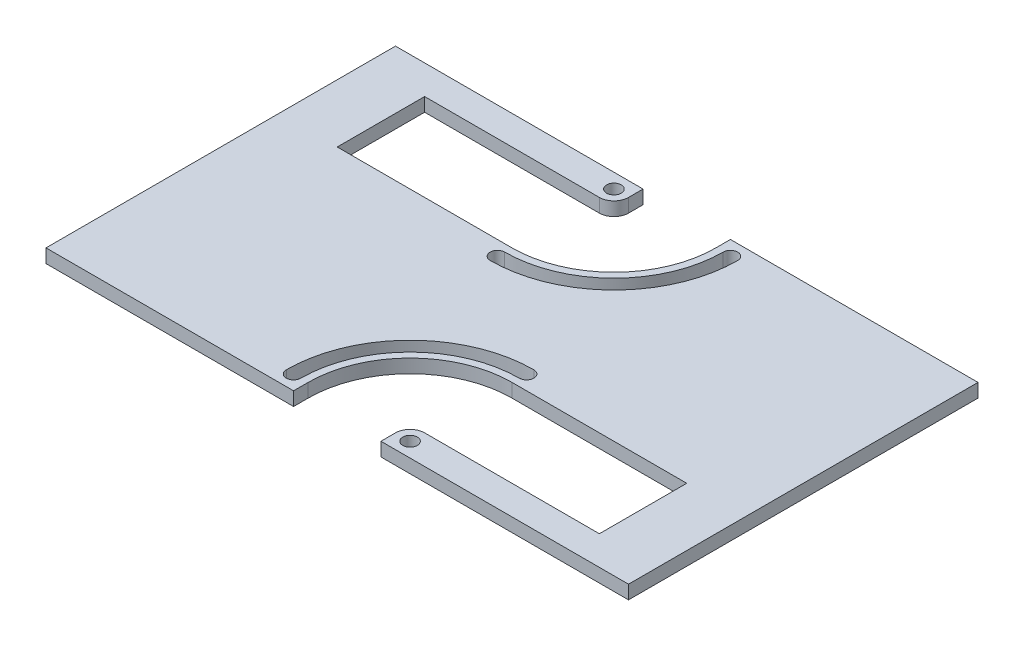
SolidWorks part; units mm, degrees
note: '?' marks a value the reader was unsure of.
ref_plane "Front Plane" through (0, 0, 0) normal (0, 0, 1) x (1, 0, 0)
ref_plane "Top Plane" through (0, 0, 0) normal (0, 1, 0) x (1, 0, 0)
ref_plane "Right Plane" through (0, 0, 0) normal (1, 0, 0) x (0, 0, -1)
sketch "Sketch2" plane through (0, 0, 0) normal (0, 1, 0) x (1, 0, 0)
  line L5 (-63.5, 38.1) -> (63.5, 38.1)
  line L6 (-63.5, 38.1) -> (-63.5, -38.1)
  line L7 (-63.5, -38.1) -> (63.5, -38.1)
  line L12 (63.5, 38.1) -> (63.5, -38.1)
  line L13 (-63.5, 38.1) -> (63.5, -38.1) construction
  line L14 (-63.5, -38.1) -> (63.5, 38.1) construction
  point P0 (0, 0)
  point P19 (-4.4901, 29.8901)
  point P20 (-40.4112, -6.0309)
  point P21 (4.4901, -29.8901)
  point P22 (40.4112, 6.0309)
  dimension "D1" = 127
  dimension "D2" = 76.2
extrude "Boss-Extrude1" add sketch "Sketch2" along normal blind 2.9718
sketch "Sketch3" plane through (0, 2.9718, 0) normal (0, 1, 0) x (1, 0, 0)
  line L0 (0, 38.1) -> (0, -38.1) construction
  line L1 (63.5, 38.1) -> (-63.5, 38.1) construction
  line L2 (-63.5, -38.1) -> (63.5, -38.1) construction
  line L3 (12.7, -9.525) -> (12.7, -34.925) construction
  line L4 (-9.525, -34.925) -> (-9.525, -38.1)
  line L5 (9.525, -34.925) -> (9.525, -38.1)
  line L6 (12.7, -12.7) -> (50.8, -12.7)
  line L7 (12.7, -31.75) -> (50.8, -31.75)
  line L8 (50.8, -31.75) -> (50.8, -12.7)
  line L9 (-9.525, -38.1) -> (9.525, -38.1)
  circle A0 centre (12.7, -34.925) radius 1.5875
  circle A1 centre (12.7, -34.925) radius 25.4 construction
  arc A2 (-14.2875, -34.925) -> (-11.1125, -34.925) centre (-12.7, -34.925) ccw
  arc A3 (12.7, -11.1125) -> (12.7, -7.9375) centre (12.7, -9.525) ccw
  arc A4 (12.7, -7.9375) -> (-14.2875, -34.925) centre (12.7, -34.925) ccw
  arc A5 (12.7, -11.1125) -> (-11.1125, -34.925) centre (12.7, -34.925) ccw
  arc A6 (12.7, -12.7) -> (-9.525, -34.925) centre (12.7, -34.925) ccw
  circle A7 centre (12.7, -34.925) radius 26.9875 construction
  circle A8 centre (12.7, -34.925) radius 23.8125 construction
  arc A9 (12.7, -31.75) -> (9.525, -34.925) centre (12.7, -34.925) ccw
  point P10 (0, -16.686)
  point P20 (36.5125, -22.225)
  point P23 (39.6875, -22.225)
  dimension "D1" = 3.175
  dimension "D4" = 50.8
  dimension "D8" = 6.35
  dimension "D9" = 44.45
  dimension "D2" = 3.175
  dimension "D3" = 12.7
  dimension "D5" = 90
  dimension "D10" = 38.1
  dimension "D6" = 1.5875
  dimension "D7" = 1.5875
extrude "Cut-Extrude1" cut sketch "Sketch3" against normal blind 2.9718
ref_axis "Axis2" through (0, -0.1486, 0) along (0, 1, 0)?
pattern_circular "CirPattern1" count 2 over 360 about axis through (0, 0, 0) along (0, 1, 0) of "Cut-Extrude1"
